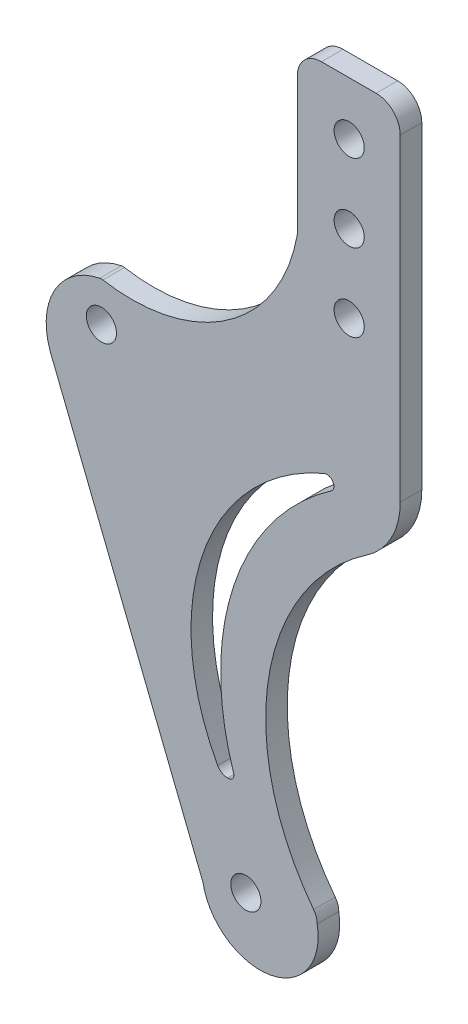
SolidWorks part; units mm, degrees
ref_plane "Front Plane" through (0, 0, 0) normal (0, 0, 1) x (1, 0, 0)
ref_plane "Top Plane" through (0, 0, 0) normal (0, 1, 0) x (1, 0, 0)
ref_plane "Right Plane" through (0, 0, 0) normal (1, 0, 0) x (0, 0, -1)
sketch "Sketch1" plane through (0, 0, 0) normal (0, 0, 1) x (1, 0, 0)
  line L0 (0, 0) -> (0, 30.156) construction
  line L1 (0, 0) -> (32.4691, 0) construction
  line L3 (-26.683, 26.3577) -> (-26.683, 6.3518)
  line L4 (-15.0841, 29.9137) -> (-23.127, 29.9137)
  line L5 (-63.1034, -26.9607) -> (-40.5959, -83.4559)
  line L7 (-11.5281, -20.4623) -> (-11.5281, 26.3577)
  line L8 (-40.5959, -83.4559) -> (-24.2809, -78.8021) construction
  circle A0 centre (-55.5441, -19.825) radius 2.2225
  circle A1 centre (-19.05, 22.085) radius 2.2225
  circle A2 centre (-19.05, -0.775) radius 2.2225
  arc A6 (-15.0841, 29.9137) -> (-11.5281, 26.3577) centre (-15.0841, 26.3577) cw
  arc A7 (-23.127, 29.9137) -> (-26.683, 26.3577) centre (-23.127, 26.3577) ccw
  arc A9 (-16.357, -29.5947) -> (-24.2809, -78.8021) centre (2.9569, -57.9465) ccw
  arc A11 (-16.357, -29.5947) -> (-11.5281, -20.4623) centre (-22.5782, -20.4623) ccw
  circle A14 centre (-34.2687, -81.6511) radius 2.2225
  arc A17 (-23.7579, -80.3848) -> (-24.2809, -78.8021) centre (-26.2976, -80.3463) ccw
  arc A21 (-40.5959, -83.4559) -> (-23.7579, -80.3848) centre (-32.1769, -81.9204) ccw
  arc A23 (-63.1034, -26.9607) -> (-55.7802, -14.0251) centre (-53.8578, -23.6541) cw
  circle A24 centre (-19.05, 10.655) radius 2.2225
  arc A25 (-55.3282, -14.0195) -> (-26.7251, 5.891) centre (-51.0844, 10.3846) ccw
  arc A26 (-55.3282, -14.0195) -> (-55.7802, -14.0251) centre (-55.5392, -15.2326) ccw
  arc A27 (-26.683, 6.3518) -> (-26.7251, 5.891) centre (-29.223, 6.3518) cw
  point P14 (-19.1056, 29.9137)
  point P24 (-15.2948, 26.5068)
  point P35 (-55.5441, -13.981)
  point P41 (-55.5441, -13.981)
  dimension "D1" = 4.445
  dimension "D2" = 2.54
  dimension "D3" = 3.556
  dimension "D4" = 34.3053
  dimension "D5" = 11.0501
  dimension "D6" = 8.5579
  dimension "D7" = 9.8191
  dimension "D11" = 11.5281
  dimension "D12" = 15.2948
  dimension "D13" = 19.05
  dimension "D10" = 2.9569
  dimension "D14" = 19.1056
  dimension "D15" = 24.2809
  dimension "D18" = 53.8578
  dimension "D19" = 55.3282
  dimension "D21" = 26.5068
  dimension "D22" = 29.9137
  dimension "D23" = 32.1769
  dimension "D24" = 34.2687
  dimension "D8" = 24.7703
  dimension "D9" = 1.2313
  dimension "D16" = 26.7251
  dimension "D17" = 23.7579
  dimension "D20" = 5.891
  dimension "D25" = 40.5959
  dimension "D26" = 10.655
  dimension "D27" = 22.085
  dimension "D28" = 20.4623
  dimension "D30" = 0.775
  dimension "D32" = 63.1034
  dimension "D36" = 19.825
extrude "Boss-Extrude1" add sketch "Sketch1" along normal blind 3.175
sketch "Sketch2" plane through (0, 0, 3.175) normal (0, 0, 1) x (1, 0, 0)
  line L3 (-36.8319, -68.3556) -> (-36.9742, -68.3556)
  line L4 (-21.446, -22.8484) -> (-21.4973, -22.7713)
  line L5 (-11.5281, -20.4623) -> (-11.5281, 26.3577) construction
  line L6 (-15.0841, 29.9137) -> (-23.127, 29.9137) construction
  arc A0 (-36.0657, -67.2962) -> (-21.6821, -24.0926) centre (0.1451, -55.3556) cw
  arc A2 (-38.4192, -67.4973) -> (-22.7361, -22.4002) centre (-10.1047, -52.0685) cw
  arc A3 (-36.0657, -67.2962) -> (-36.8319, -68.3556) centre (-36.8319, -67.5489) cw
  arc A4 (-38.4192, -67.4973) -> (-36.9742, -68.3556) centre (-36.9742, -66.7099) ccw
  arc A5 (-21.4973, -22.7713) -> (-22.7361, -22.4002) centre (-22.3398, -23.3309) ccw
  arc A6 (-21.446, -22.8484) -> (-21.6821, -24.0926) centre (-22.2007, -23.3497) cw
  arc A8 (-16.357, -29.5947) -> (-24.2809, -78.8021) centre (2.9569, -57.9465) ccw construction
  point P6 (-37.4679, -64.5901)
  point P7 (-37.7065, -64.6134)
  point P14 (-21.9563, -22.0802)
  point P17 (-20.9505, -23.5944)
  dimension "D2" = 32.2453
  dimension "D3" = 0.8067
  dimension "D4" = 1.6457
  dimension "D5" = 1.0115
  dimension "D1" = 38.1287
  dimension "D6" = 0.906
  dimension "D7" = 1.4234
  dimension "D8" = 11.6732
  dimension "D9" = 9.4224
  dimension "D10" = 9.9691
  dimension "D11" = 24.5376
extrude "Cut-Extrude3" cut sketch "Sketch2" against normal through all
